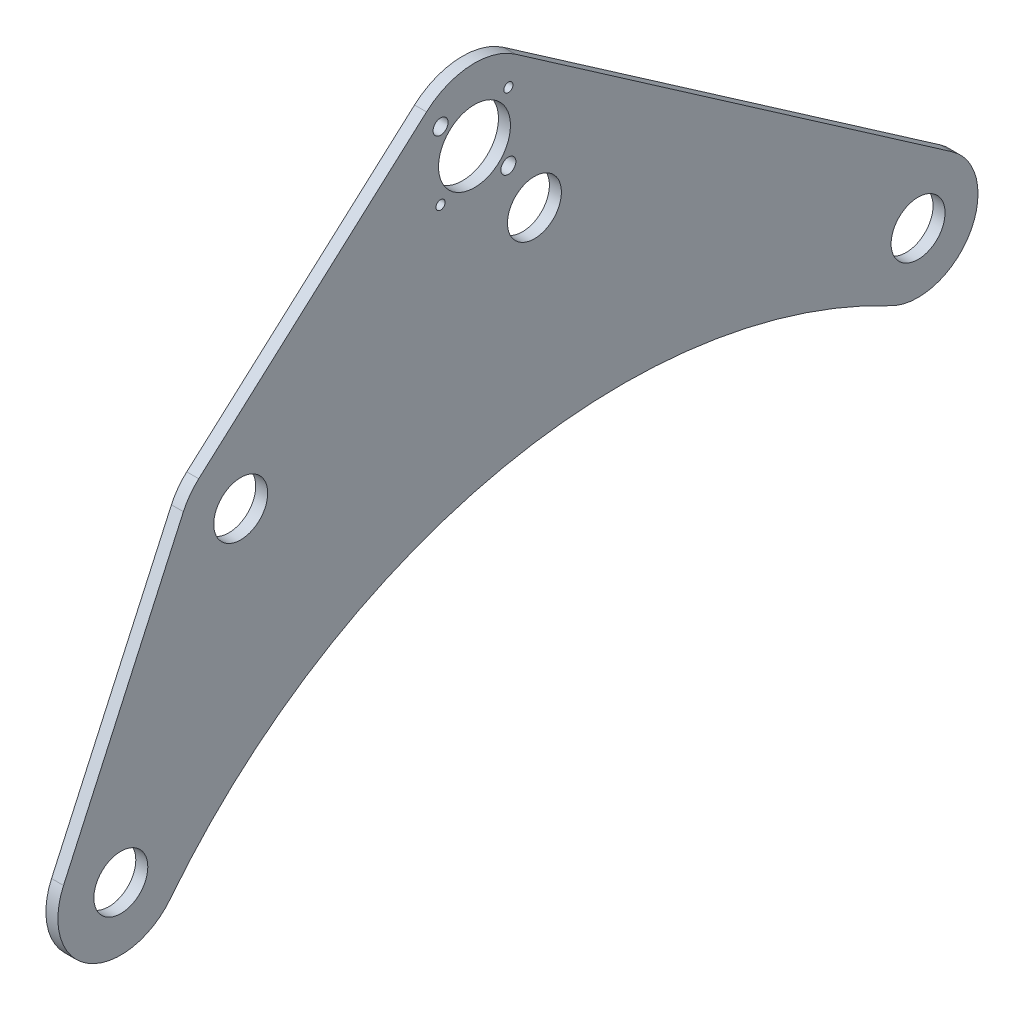
SolidWorks part; units mm, degrees
material "Acrylic (Medium-high impact)"
ref_plane "Front Plane" through (0, 0, 0) normal (0, 0, 1) x (1, 0, 0)
ref_plane "Top Plane" through (0, 0, 0) normal (0, 1, 0) x (1, 0, 0)
ref_plane "Right Plane" through (0, 0, 0) normal (1, 0, 0) x (0, 0, -1)
sketch "Sketch1" plane through (0, 0, 0) normal (1, 0, 0) x (0, 0, -1)
  line L0 (-548.7618, -304.8) -> (152.435, -304.8)
  line L1 (-192.8252, -101.6) -> (-152.4, -101.6)
  line L2 (-234.95, -143.7248) -> (-234.95, -186.4752)
  line L3 (-192.8252, -228.6) -> (-152.4, -228.6)
  line L4 (-152.4, -101.6) -> (-152.4, -228.6)
  circle A1 centre (0, 0) radius 6.35
  circle A6 centre (-422.275, -88.9) radius 9.525
  circle A7 centre (-358.775, 50.8) radius 9.525
  circle A8 centre (-203.2, 111.125) radius 9.525
  arc A9 (-234.95, -186.4752) -> (-192.8252, -228.6) centre (-192.8252, -186.4752) ccw
  arc A10 (-192.8252, -101.6) -> (-234.95, -143.7248) centre (-192.8252, -143.7248) ccw
  circle A11 centre (-358.775, -186.4752) radius 120.65
  circle A12 centre (-234.95, 155.194) radius 29.845
  point P18 (-203.2, 18.1715)
  point P22 (-358.775, -186.4752)
  point P23 (-269.3773, 0)
  point P24 (-358.775, -186.4752)
  point P25 (-192.8252, 0)
  point P26 (-349.8091, -304.8)
  point P27 (-937.439, -304.8)
  point P28 (-943.2832, -304.8)
  point P29 (-336.2918, -48.9395)
  point P30 (-358.775, -186.4752)
  point P31 (0, 0)
  dimension "D1" = 12.7
  dimension "D2" = 19.05
  dimension "D3" = 42.1248
  dimension "D4" = 127
  dimension "D7" = 203.2
  dimension "D6" = 241.3
  dimension "D16" = 59.69
  dimension "D5" = 82.55
  dimension "D8" = 304.8
  dimension "D9" = 152.4
  dimension "D10" = 422.275
  dimension "D11" = 88.9
  dimension "D12" = 358.775
  dimension "D13" = 50.8
  dimension "D14" = 203.2
  dimension "D15" = 111.125
  dimension "D17" = 234.95
  dimension "D18" = 155.194
sketch "Sketch2" plane through (0, 0, 0) normal (1, 0, 0) x (0, 0, -1)
  line L1 (-452.6243, -75.1048) -> (-389.1243, 64.5952)
  line L3 (-381.0036, 75.6451) -> (-260.3541, 183.5884)
  line L5 (-213.2394, 186.5031) -> (18.0922, 26.0909)
  arc A0 (-381.0036, 75.6451) -> (-389.1243, 64.5952) centre (-358.775, 50.8) ccw
  arc A2 (-452.6243, -75.1048) -> (-396.0719, -109.5104) centre (-422.275, -88.9) ccw
  arc A4 (-213.2394, 186.5031) -> (-260.3541, 183.5884) centre (-234.95, 155.194) ccw
  arc A5 (-14.7643, -28.1083) -> (18.0922, 26.0909) centre (0, 0) ccw
  arc A8 (-396.0719, -109.5104) -> (-14.7643, -28.1083) centre (-156.5012, -297.9484) cw
  circle A12 centre (-422.275, -88.9) radius 9.525 construction
  circle A13 centre (-358.775, 50.8) radius 9.525 construction
  dimension "D1" = 33.3375
  dimension "D2" = 63.5
  dimension "D3" = 76.2
  dimension "D4" = 304.8
extrude "Boss-Extrude1" add sketch "Sketch2" along normal blind 6.35
sketch "Sketch3" plane through (6.35, 0, 0) normal (1, 0, 0) x (0, 0, -1)
  line L0 (-216.9895, 173.1545) -> (-252.9105, 137.2335) construction
  line L1 (-234.95, 155.194) -> (-234.95, 205.0182) construction
  line L2 (-252.9105, 173.1545) -> (-216.9895, 137.2335) construction
  circle A0 centre (-203.2, 111.125) radius 14.2875
  circle A1 centre (-358.775, 50.8) radius 14.2875
  circle A2 centre (-422.275, -88.9) radius 14.2875
  circle A3 centre (-234.95, 155.194) radius 19.05
  circle A4 centre (0, 0) radius 14.2875
  circle A5 centre (-252.9105, 137.2335) radius 2.413
  circle A7 centre (-216.9895, 137.2335) radius 3.9687
  circle A8 centre (-216.9895, 173.1545) radius 2.413
  circle A9 centre (-252.9105, 173.1545) radius 3.9687
  point P18 (-234.95, 155.194)
  point P28 (-234.95, 155.194)
  dimension "D1" = 38.1
  dimension "D2" = 28.575
  dimension "D3" = 4.826
  dimension "D4" = 50.8
  dimension "D5" = 45
  dimension "D6" = 7.9375
  dimension "D7" = 50.8
extrude "Cut-Extrude1" cut sketch "Sketch3" against normal up to next
